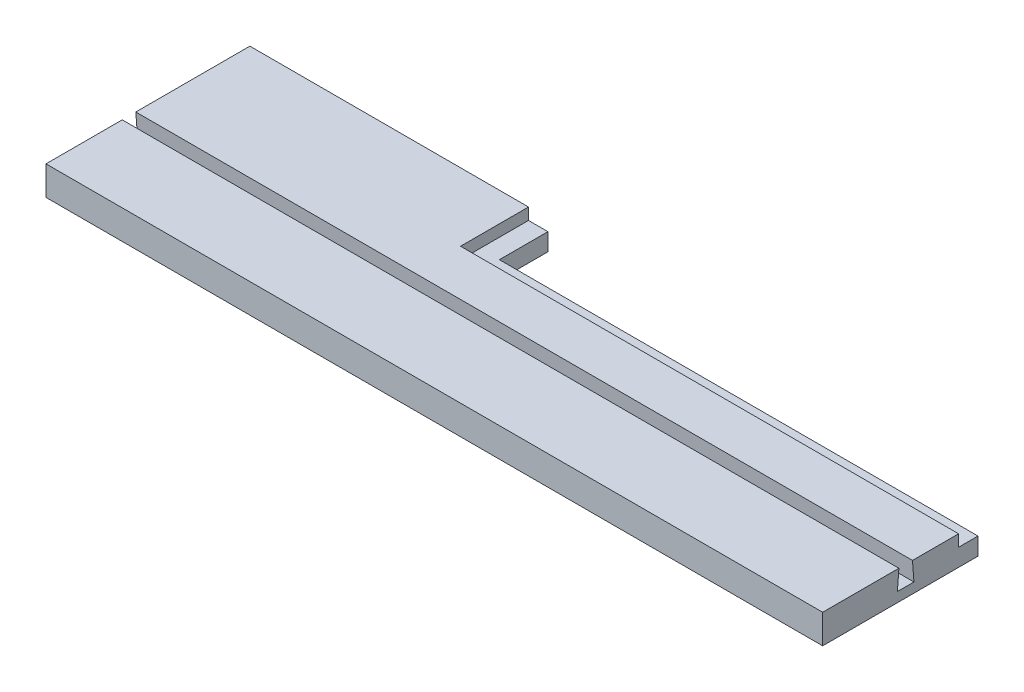
SolidWorks part; units mm, degrees
ref_plane "Front Plane" through (0, 0, 0) normal (0, 0, 1) x (1, 0, 0)
ref_plane "Top Plane" through (0, 0, 0) normal (0, 1, 0) x (1, 0, 0)
ref_plane "Right Plane" through (0, 0, 0) normal (1, 0, 0) x (0, 0, -1)
sketch "Sketch1" plane through (0, 0, 0) normal (0, 1, 0) x (1, 0, 0)
  line L1 (-7.5455, 9.1364) -> (72.4545, 9.1364)
  line L2 (-7.5455, 9.1364) -> (-7.5455, -4.8636)
  line L3 (-7.5455, -4.8636) -> (72.4545, -4.8636)
  line L4 (72.4545, 9.1364) -> (72.4545, -4.8636)
  dimension "D1" = 14
  dimension "D2" = 80
extrude "Boss-Extrude1" add sketch "Sketch1" along normal blind 2
sketch "Sketch2" plane through (0, 2, 0) normal (0, 1, 0) x (1, 0, 0)
  line L0 (72.4545, -4.8636) -> (72.4545, 9.1364) construction
  line L1 (-7.5455, -4.8636) -> (72.4545, -4.8636)
  line L2 (-7.5455, -4.8636) -> (-7.5455, 2.8364)
  line L3 (-7.5455, 2.8364) -> (72.4545, 2.8364)
  line L4 (72.4545, -4.8636) -> (72.4545, 2.8364)
  line L7 (-7.5455, 9.1364) -> (72.4545, 9.1364)
  line L8 (-7.5455, 9.1364) -> (-7.5455, 4.5364)
  line L9 (-7.5455, 4.5364) -> (72.4545, 4.5364)
  line L10 (72.4545, 9.1364) -> (72.4545, 4.5364)
  dimension "D1" = 7.7
  dimension "D2" = 1.7
  dimension "D3" = 4.6
extrude "Boss-Extrude2" add sketch "Sketch2" along normal blind 2 contours L3 L4 L1 L2 | L8 L9 L10 L7
sketch "Sketch3" plane through (0, 0, 0) normal (0, -1, 0) x (1, 0, 0)
  line L0 (72.4545, 4.8636) -> (72.4545, -9.1364) construction
  line L1 (-7.5455, -9.1364) -> (21.1545, -9.1364)
  line L2 (-7.5455, -9.1364) -> (-7.5455, -16.1364)
  line L3 (-7.5455, -16.1364) -> (21.1545, -16.1364)
  line L4 (21.1545, -9.1364) -> (21.1545, -16.1364)
  dimension "D1" = 7
  dimension "D2" = 51.3
extrude "Boss-Extrude3" add sketch "Sketch3" against normal up to surface (4 mm away) up to face at (32.4545, 4, -6.8364)
sketch "Sketch4" plane through (-7.5455, 0, 0) normal (-1, 0, 0) x (0, 0, 1)
  line L0 (-4.5364, 4) -> (-2.8364, 4) construction
  line L1 (-2.8364, 2) -> (-2.9864, 4)
  line L2 (-2.9864, 4) -> (-2.8364, 4)
  line L3 (-2.8364, 4) -> (-2.8364, 2)
  line L4 (-4.5364, 2) -> (-4.5364, 4)
  line L5 (-4.5364, 4) -> (-4.3864, 4)
  line L6 (-4.3864, 4) -> (-4.5364, 2)
  dimension "D1" = 0.15
  dimension "D2" = 0.15
extrude "Boss-Extrude4" add sketch "Sketch4" against normal up to surface (80 mm away) up to face at (72.4545, 2.5, -2.9114)
sketch "Sketch5" plane through (0, 0, 0) normal (0, -1, 0) x (1, 0, 0)
  line L0 (-7.5455, 4.8636) -> (72.4545, 4.8636)
  line L1 (72.4545, 4.8636) -> (72.4545, -9.1364)
  line L2 (72.4545, -9.1364) -> (21.1545, -9.1364)
  line L3 (21.1545, -9.1364) -> (21.1545, -16.1364)
  line L4 (21.1545, -16.1364) -> (-7.5455, -16.1364)
  line L5 (-7.5455, -16.1364) -> (-7.5455, 4.8636)
extrude "Cut-Extrude1" cut sketch "Sketch5" against normal blind 1
sketch "Sketch6" plane through (0, 1, 0) normal (0, -1, 0) x (1, 0, 0)
  line L1 (21.1545, -9.1364) -> (72.4545, -9.1364)
  line L2 (21.1545, -9.1364) -> (21.1545, -11.1364)
  line L3 (23.1545, -11.1364) -> (72.4545, -11.1364)
  line L4 (72.4545, -9.1364) -> (72.4545, -11.1364)
  line L5 (21.1545, -16.1364) -> (23.1545, -16.1364)
  line L6 (21.1545, -16.1364) -> (21.1545, -11.1364)
  line L8 (23.1545, -16.1364) -> (23.1545, -11.1364)
  line L9 (72.4545, -9.1364) -> (72.4545, 4.8636) construction
  dimension "D1" = 2
  dimension "D2" = 2
  dimension "D3" = 0
extrude "Boss-Extrude5" add sketch "Sketch6" against normal blind 1.8
